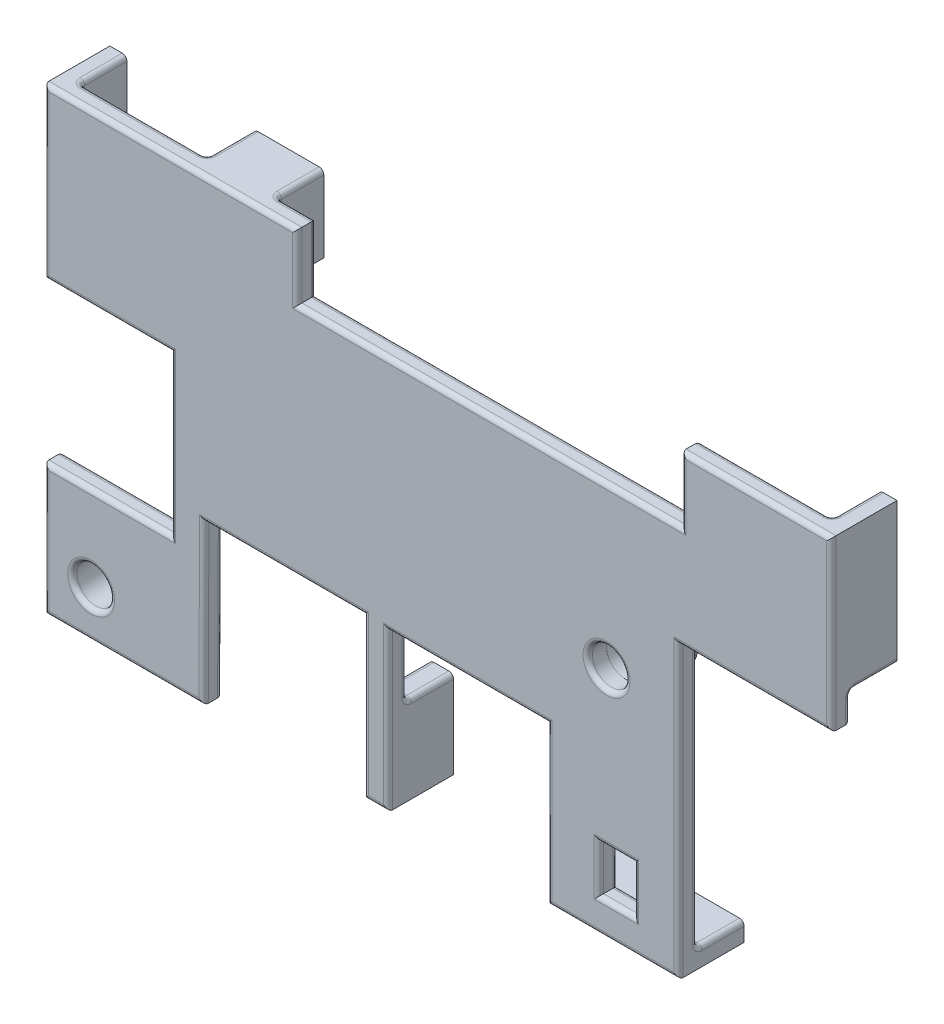
SolidWorks part; units mm, degrees
ref_plane "Front Plane" through (0, 0, 0) normal (1, 0, 0) x (0, 1, 0)
ref_plane "Top Plane" through (0, 0, 0) normal (0, 0, 1) x (0, 1, 0)
ref_plane "Right Plane" through (0, 0, 0) normal (0, 1, 0) x (-1, 0, 0)
sketch "Sketch1" plane through (0, 0, 0) normal (0, 0, 1) x (0, 1, 0)
  line L0 (-6.3862, 38.6703) -> (-6.3862, 25.151)
  line L2 (-20.3862, 38.6703) -> (-20.3862, 21.6703)
  line L3 (10.6138, -45.3297) -> (28.6138, -45.3297)
  line L4 (28.6138, 38.6703) -> (28.6138, 11.6703)
  line L5 (-6.3862, 25.151) -> (10.6138, 25.151)
  line L6 (10.6138, 25.151) -> (10.6138, 38.6703)
  line L7 (-20.3862, 38.6703) -> (-6.3862, 38.6703)
  line L8 (-20.3862, 38.6703) -> (28.6138, 38.6703) construction
  line L9 (10.6138, 38.6703) -> (28.6138, 38.6703)
  line L10 (-20.3862, 21.6703) -> (-3.3862, 21.5903)
  line L11 (13.1138, 21.5903) -> (-17.8862, 21.5903) construction
  line L12 (-3.3862, 21.5903) -> (-3.3862, 4.5903)
  line L13 (-3.3862, 4.5903) -> (-20.3862, 4.5903)
  line L14 (-3.6077, -15.0097) -> (-20.3862, -15.0097)
  line L15 (-20.3862, 1.9903) -> (-3.6077, 1.9903)
  line L16 (-3.6077, 1.9903) -> (-3.6077, -15.0097)
  line L17 (28.6138, 11.6703) -> (21.6138, 11.6703)
  line L18 (-20.3862, 4.5903) -> (-20.3862, 1.9903)
  line L19 (21.6138, 11.6703) -> (21.6138, -29.3297)
  line L20 (-20.3862, -45.3297) -> (-20.3862, 38.6703) construction
  line L23 (21.6138, -29.3297) -> (28.6138, -29.3297)
  line L24 (28.6138, -29.3297) -> (28.6138, -45.3297)
  line L25 (10.6138, -45.3297) -> (10.6138, -29.0097)
  line L28 (-16.8862, -20.5097) -> (-11.8862, -20.5097)
  line L29 (-11.8862, -20.5097) -> (-11.8862, -24.2597)
  line L30 (-11.8862, -24.2597) -> (-16.8862, -24.2597)
  line L31 (-20.3862, -15.0097) -> (-20.3862, -29.0097)
  line L32 (-16.8862, -20.5097) -> (-16.8862, -24.2597)
  line L33 (-20.3862, -29.0097) -> (10.6138, -29.0097)
  circle A0 centre (-15.3862, 33.6703) radius 2
  circle A1 centre (4.6138, -21.3297) radius 2
  dimension "D1" = 4
  dimension "D2" = 4
  dimension "D3" = 3.5
  dimension "D4" = 17
  dimension "D5" = 17
  dimension "D6" = 17
  dimension "D7" = 2.6
  dimension "D8" = 17
  dimension "D9" = 5
  dimension "D10" = 14
  dimension "D11" = 17
  dimension "D12" = 18
  dimension "D13" = 27
  dimension "D14" = 41
  dimension "D15" = 16
  dimension "D16" = 18
  dimension "D17" = 3.75
  dimension "D18" = 4.75
  dimension "D19" = 7
extrude "Boss-Extrude1" add sketch "Sketch1" along normal blind 2
sketch "Sketch3" plane through (0, 0, 0) normal (0, 0, -1) x (1, 0, 0)
  line L13 (-4.5903, 20.3862) -> (-1.9903, 20.3862)
  line L14 (-4.5903, 20.3862) -> (-4.5903, 11.0551)
  line L15 (-4.5903, 11.0551) -> (-1.9903, 11.0551)
  line L16 (-1.9903, 20.3862) -> (-1.9903, 11.0551)
  line L17 (-1.9903, 20.3862) -> (-1.9903, 3.6077) construction
  line L19 (-38.6703, -28.6138) -> (-36.8509, -28.6138)
  line L20 (-38.6703, -28.6138) -> (-38.6703, -16.4934)
  line L21 (-38.6703, -16.4934) -> (-36.8509, -16.4934)
  line L22 (-36.8509, -28.6138) -> (-36.8509, -16.4934)
  line L23 (-11.6703, -28.6138) -> (-38.6703, -28.6138) construction
  line L24 (-23.3211, -28.6138) -> (-15.8388, -28.6138)
  line L25 (-23.3211, -28.6138) -> (-23.3211, -20.4396)
  line L26 (-23.3211, -20.4396) -> (-15.8388, -20.4396)
  line L27 (-15.8388, -28.6138) -> (-15.8388, -20.4396)
  line L28 (45.3297, -10.6138) -> (45.3297, -28.6138) construction
  line L29 (45.3297, -28.6138) -> (43.393, -28.6138)
  line L30 (45.3297, -28.6138) -> (45.3297, -13.4845)
  line L31 (45.3297, -13.4845) -> (43.393, -13.4845)
  line L32 (43.393, -28.6138) -> (43.393, -13.4845)
  line L33 (45.3297, -28.6138) -> (29.3297, -28.6138) construction
  line L34 (31.6176, -13.4845) -> (45.3297, -13.4845) construction
  line L36 (15.0097, 20.3862) -> (29.0097, 20.3862)
  line L37 (15.0097, 20.3862) -> (15.0097, 18.3862)
  line L38 (15.0097, 18.3862) -> (29.0097, 18.3862)
  line L39 (29.0097, 20.3862) -> (29.0097, 18.3862)
  circle A5 centre (-33.6703, 15.3862) radius 2
  circle A6 centre (-33.6703, 15.3862) radius 3
  circle A8 centre (21.343, -4.6376) radius 2.1171
  circle A10 centre (21.343, -4.6376) radius 3.0333
  dimension "D1" = 6
  dimension "D2" = 2
extrude "Boss-Extrude2" add sketch "Sketch3" along normal blind 5
fillet "Fillet10" radius 0.5 76 edges at (18.3097, 4.6376, -5) (-36.6703, -15.3862, -5) (23.3297, 4.6138, 2) (-31.6703, -15.3862, 2) (-31.9106, -6.3862, 2) (-25.151, 2.1138, 2) (-31.9106, 10.6138, 2) (-38.6703, 19.6138, 2) (-25.1703, 28.6138, 2) (-11.6703, 25.1138, 2) (8.8297, 21.6138, 2) (29.3297, 25.1138, 2) (37.3297, 28.6138, 2) (45.3297, 19.6138, 2) (37.1697, 10.6138, 2) (6.5097, -3.6077, 2) (-1.9903, -11.997, 2) (-3.2903, -20.3862, 2) (-4.5903, -11.8862, 2) (-13.0903, -3.3862, 2) (-21.6303, -11.8862, 2) (-30.1703, -20.3862, 2) (-38.6703, -13.3862, 2) (-30.1703, -20.3862, 0) (-21.6303, -11.8862, 0) (-13.0903, -3.3862, 0) (-4.5903, -7.2206, 0) (-1.9903, -7.3314, 0) (6.5097, -3.6077, 0) (37.1697, 10.6138, 0) (45.3297, 12.0491, 0) (36.3614, 28.6138, 0) (29.3297, 25.1138, 0) (8.8297, 21.6138, 0) (-11.6703, 25.1138, 0) (-13.7545, 28.6138, 0) (-38.6703, 13.5536, 0) (-31.9106, 10.6138, 0) (-25.151, 2.1138, 0) (-31.9106, -6.3862, 0) (-38.6703, -13.3862, 0) (18.3097, 4.6376, 0) (-36.6703, -15.3862, 0) (15.0097, -11.997, 2) (15.0097, -10.997, 0) (24.2597, -14.3862, 2) (22.3847, -11.8862, 2) (20.5097, -14.3862, 2) (20.5097, -14.3862, 0) (22.3847, -11.8862, 0) (24.2597, -14.3862, 0) (43.393, 28.6138, -2.5) (-15.8388, 28.6138, -2.5) (-23.3211, 28.6138, -2.5) (-36.8509, 28.6138, -2.5) (-38.6703, 16.4934, -2.5) (-4.5903, -11.0551, -2.5) (-1.9903, -11.0551, -2.5) (45.3297, 13.4845, -2.5) (-15.8388, 24.5267, 0) (-19.5799, 20.4396, 0) (-23.3211, 24.5267, 0) (-30.086, 28.6138, 0) (-36.8509, 22.5536, 0) (-37.7606, 16.4934, 0) (-3.2903, -11.0551, 0) (44.3614, 13.4845, 0) (43.393, 21.0491, 0) (29.0097, -18.3862, -2.5) (15.0097, -18.3862, -2.5) (22.3847, -16.8862, 2) (22.0097, -20.3862, 2) (22.3847, -16.8862, 0) (22.0097, -18.3862, 0) (29.0097, -4.8862, 2) (29.0097, -3.8862, 0)
